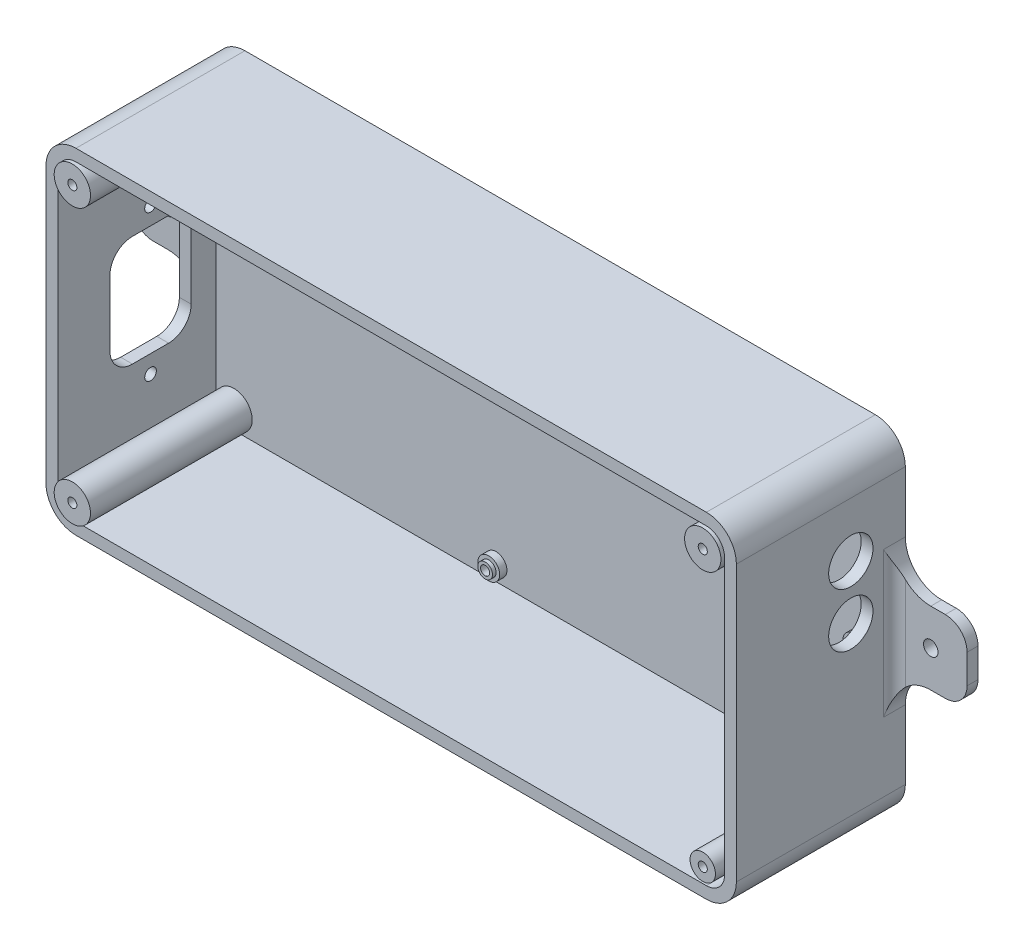
SolidWorks part; units mm, degrees
ref_plane "Front Plane" through (0, 0, 0) normal (0, 0, 1) x (1, 0, 0)
ref_plane "Top Plane" through (0, 0, 0) normal (0, 1, 0) x (1, 0, 0)
ref_plane "Right Plane" through (0, 0, 0) normal (1, 0, 0) x (0, 0, -1)
sketch "Sketch1" plane through (0, 0, 0) normal (0, 0, 1) x (1, 0, 0)
  line L0 (-68.41, 24.13) -> (105.09, 24.13)
  line L5 (-68.41, 20.88) -> (105.09, 20.88)
  line L6 (-73.41, 15.88) -> (-73.41, -59.87)
  line L7 (-68.41, -64.87) -> (105.09, -64.87)
  line L8 (110.09, 15.88) -> (110.09, -59.87)
  line L13 (113.34, 15.88) -> (113.34, -59.87)
  line L14 (-68.41, -68.12) -> (105.09, -68.12)
  line L15 (-76.66, 15.88) -> (-76.66, -59.87)
  line L16 (-73.66, 15.88) -> (-73.66, -59.87)
  line L17 (-68.41, -65.12) -> (105.09, -65.12)
  line L18 (110.34, 15.88) -> (110.34, -59.87)
  line L19 (-68.41, 21.13) -> (105.09, 21.13)
  line L25 (90.16, -25.08) -> (108.69, -25.08)
  line L26 (90.16, -25.08) -> (90.16, -55.87)
  line L27 (90.16, -55.87) -> (108.69, -55.87)
  line L28 (108.69, -25.08) -> (108.69, -55.87)
  line L29 (-0.2, 20.73) -> (88.16, 20.73)
  line L30 (-0.2, 20.73) -> (-0.2, -64.62)
  line L31 (-0.2, -64.62) -> (88.16, -64.62)
  line L32 (88.16, 20.73) -> (88.16, -64.62)
  line L33 (-44.52, 0.47) -> (-1.2, 0.47)
  line L34 (-44.52, 0.47) -> (-44.52, -63.87)
  line L35 (-44.52, -63.87) -> (-1.2, -63.87)
  line L36 (-1.2, 0.47) -> (-1.2, -63.87)
  circle A13 centre (-68.41, 15.88) radius 1.25
  circle A14 centre (105.09, 15.88) radius 1.25
  circle A15 centre (105.09, -59.87) radius 1.25
  circle A16 centre (-68.41, -59.87) radius 1.25
  arc A17 (-73.41, -59.87) -> (-68.41, -64.87) centre (-68.41, -59.87) ccw
  arc A18 (105.09, -64.87) -> (110.09, -59.87) centre (105.09, -59.87) ccw
  arc A19 (105.09, 20.88) -> (110.09, 15.88) centre (105.09, 15.88) cw
  arc A20 (-68.41, 20.88) -> (-73.41, 15.88) centre (-68.41, 15.88) ccw
  arc A21 (105.09, 24.13) -> (113.34, 15.88) centre (105.09, 15.88) cw
  arc A22 (105.09, -68.12) -> (113.34, -59.87) centre (105.09, -59.87) ccw
  arc A23 (-76.66, -59.87) -> (-68.41, -68.12) centre (-68.41, -59.87) ccw
  arc A24 (-68.41, 24.13) -> (-76.66, 15.88) centre (-68.41, 15.88) ccw
  circle A27 centre (105.09, -59.87) radius 3.5
  arc A29 (-73.66, -59.87) -> (-68.41, -65.12) centre (-68.41, -59.87) ccw
  arc A30 (105.09, -65.12) -> (110.34, -59.87) centre (105.09, -59.87) ccw
  arc A31 (105.09, 21.13) -> (110.34, 15.88) centre (105.09, 15.88) cw
  arc A32 (-68.41, 21.13) -> (-73.66, 15.88) centre (-68.41, 15.88) ccw
  circle A46 centre (104.265, -29.095) radius 2.375
  circle A47 centre (104.265, -51.465) radius 2.375
  circle A48 centre (104.265, -29.095) radius 2.175
  circle A49 centre (104.265, -51.465) radius 2.175
  circle A50 centre (104.265, -29.095) radius 1.25
  circle A51 centre (104.265, -51.465) radius 1.25
  circle A52 centre (83.915, -60.695) radius 2.225
  circle A53 centre (83.915, -14.675) radius 2.225
  circle A54 centre (3.695, -14.675) radius 2.225
  circle A55 centre (3.695, -60.695) radius 2.225
  circle A56 centre (3.695, -14.675) radius 2.025
  circle A57 centre (83.915, -14.675) radius 2.025
  circle A58 centre (83.915, -60.695) radius 2.025
  circle A59 centre (3.695, -60.695) radius 2.025
  circle A60 centre (3.695, -14.675) radius 1.25
  circle A61 centre (83.915, -14.675) radius 1.25
  circle A62 centre (83.915, -60.695) radius 1.25
  circle A63 centre (3.695, -60.695) radius 1.25
  circle A64 centre (105.09, 15.88) radius 5
  circle A65 centre (-68.41, 15.88) radius 5
  circle A66 centre (-68.41, -59.87) radius 5
  circle A67 centre (3.695, -14.675) radius 3
  circle A68 centre (83.915, -14.675) radius 3
  circle A69 centre (104.265, -29.095) radius 3.1359
  circle A70 centre (104.265, -51.465) radius 3.4191
  circle A71 centre (83.915, -60.695) radius 3
  circle A72 centre (3.695, -60.695) radius 3
  point P49 (-73.41, -64.87)
  point P58 (110.09, 20.88)
  point P61 (-73.41, 20.88)
  dimension "D3" = 73.41
  dimension "D6" = 18.53
  dimension "D7" = 30.79
  dimension "D8" = 4.75
  dimension "D9" = 4.75
  dimension "D10" = 4.425
  dimension "D11" = 4.015
  dimension "D12" = 4.405
  dimension "D13" = 0.2
  dimension "D14" = 2.5
  dimension "D15" = 2.5
  dimension "D16" = 2.5
  dimension "D17" = 2.5
  dimension "D18" = 2.5
  dimension "D19" = 2.5
  dimension "D49" = 5
  dimension "D51" = 6
  dimension "D52" = 7
  dimension "D53" = 6
  dimension "D54" = 6
  dimension "D26" = 4.45
  dimension "D27" = 4.45
  dimension "D28" = 4.45
  dimension "D29" = 4.45
  dimension "D35" = 2.5
  dimension "D36" = 2.5
  dimension "D37" = 2.5
  dimension "D38" = 2.5
  dimension "D55" = 6
  dimension "D2" = 20.88
  dimension "D20" = 1.4
  dimension "D21" = 9
  dimension "D22" = 88.36
  dimension "D23" = 85.35
  dimension "D24" = 2
  dimension "D25" = 0.25
  dimension "D30" = 4.245
  dimension "D31" = 3.895
  dimension "D32" = 3.925
  dimension "D33" = 46.02
  dimension "D34" = 0.2
  dimension "D39" = 43.32
  dimension "D40" = 64.34
  dimension "D41" = 1
  dimension "D42" = 183.5
  dimension "D43" = 85.75
  dimension "D44" = 5
  dimension "D45" = 5
  dimension "D46" = 5
  dimension "D47" = 5
  dimension "D48" = 1
  dimension "D50" = 3.25
  dimension "D56" = 3
extrude "Boss-Extrude1" add sketch "Sketch1" along normal blind 3 contours L0 A21 L13 A22 L14 A23 L15 A24
extrude "Boss-Extrude5" add sketch "Sketch1<9>" along normal blind 43.5 from surface contours L7 A18 L8 A19 L5 A20 L6 A17 | L14 A22 L13 A21 L0 A24 L15 A23 starting at face at (18.34, -21.995, 3)
sketch "Sketch1<9>" plane through (0, 0, 0) normal (0, 0, 1) x (1, 0, 0) same geometry as "Sketch1"
extrude "Boss-Extrude6" add sketch "Sketch1<10>" along normal blind 44.5 from surface contours A66 | A65 | A64 | A27 starting at face at (18.34, -21.995, 3)
sketch "Sketch1<10>" plane through (0, 0, 0) normal (0, 0, 1) x (1, 0, 0) same geometry as "Sketch1"
extrude "Boss-Extrude7" add sketch "Sketch1<11>" along normal blind 3 from surface contours A48 | A49 | A57 | A58 | A59 | A56 starting at face at (108.59, -59.87, 3)
sketch "Sketch1<11>" plane through (0, 0, 0) normal (0, 0, 1) x (1, 0, 0) same geometry as "Sketch1"
extrude "Boss-Extrude8" add sketch "Sketch1<12>" along normal blind 2 from surface contours A67 | A72 | A71 | A68 | A69 | A70 starting at face at (5.72, -14.675, 3)
sketch "Sketch1<12>" plane through (0, 0, 0) normal (0, 0, 1) x (1, 0, 0) same geometry as "Sketch1"
extrude "Cut-Extrude7" cut sketch "Sketch1<13>" along normal through all both and the other way through all contours A60 | A63 | A16 | A13 | A61 | A14 | A50 | A51 | A62 | A15
sketch "Sketch1<13>" plane through (0, 0, 0) normal (0, 0, 1) x (1, 0, 0) same geometry as "Sketch1"
sketch "Sketch3" plane through (-76.66, 0, 0) normal (-1, 0, 0) x (0, 0, 1)
  line L0 (32.16, -15.84) -> (32.16, -33.87)
  line L1 (25.96, -9.84) -> (16, -9.84)
  line L2 (31.96, -15.84) -> (31.96, -33.87)
  line L3 (25.96, -39.87) -> (16, -39.87)
  line L4 (10, -15.84) -> (10, -33.87)
  line L5 (25.96, -40.07) -> (16, -40.07)
  line L6 (9.8, -15.84) -> (9.8, -33.87)
  line L7 (25.96, -9.64) -> (16, -9.64)
  line L8 (0, 15.88) -> (0, -59.87) construction
  line L9 (46.5, -59.87) -> (0, -59.87) construction
  arc A0 (16, -39.87) -> (10, -33.87) centre (16, -33.87) cw
  arc A1 (16, -9.84) -> (10, -15.84) centre (16, -15.84) ccw
  arc A2 (25.96, -9.84) -> (31.96, -15.84) centre (25.96, -15.84) cw
  arc A3 (31.96, -33.87) -> (25.96, -39.87) centre (25.96, -33.87) cw
  circle A4 centre (20.98, -44.95) radius 1.6
  circle A5 centre (20.98, -4.76) radius 1.6
  arc A6 (32.16, -33.87) -> (25.96, -40.07) centre (25.96, -33.87) cw
  arc A7 (16, -40.07) -> (9.8, -33.87) centre (16, -33.87) cw
  arc A8 (16, -9.64) -> (9.8, -15.84) centre (16, -15.84) ccw
  arc A9 (25.96, -9.64) -> (32.16, -15.84) centre (25.96, -15.84) cw
  point P8 (10, -9.84)
  point P11 (31.96, -9.84)
  point P14 (31.96, -39.87)
  point P19 (0, 0)
  point P20 (0, 0)
  point P21 (0, 0)
  point P24 (29.5662, -30.03)
  dimension "D3" = 6
  dimension "D4" = 3.2
  dimension "D5" = 3.2
  dimension "D1" = 21.96
  dimension "D2" = 30.03
  dimension "D6" = 40.19
  dimension "D7" = 5.08
  dimension "D8" = 10.98
  dimension "D10" = 10
  dimension "D11" = 20
  dimension "D9" = 0.2
extrude "Cut-Extrude8" cut sketch "Sketch3" against normal up to next and the other way through all contours A5 | A4 | L5 A7 L6 A8 L7 A9 L0 A6
sketch "Sketch4" plane through (113.34, 0, 0) normal (1, 0, 0) x (0, 0, -1)
  line L0 (-46.5, 15.88) -> (0, 15.88) construction
  line L1 (0, 15.88) -> (0, -59.87) construction
  circle A0 centre (-15, 0.88) radius 4.16
  circle A1 centre (-15, -14.05) radius 4.16
  circle A2 centre (-15, 0.88) radius 6.1
  circle A3 centre (-15, -14.05) radius 6.1
  dimension "D1" = 8.32
  dimension "D2" = 8.32
  dimension "D4" = 12.2
  dimension "D5" = 12.2
  dimension "D3" = 14.93
  dimension "D6" = 15
  dimension "D7" = 15
extrude "Cut-Extrude9" cut sketch "Sketch4" against normal up to next contours A3 | A2
sketch "Sketch5" plane through (0, 0, 0) normal (0, 0, -1) x (-1, 0, 0)
  line L0 (76.66, 15.88) -> (76.66, -59.87) construction
  line L1 (76.66, -10.87) -> (90.66, -10.87)
  line L2 (76.66, -10.87) -> (76.66, -30.87)
  line L3 (76.66, -30.87) -> (90.66, -30.87)
  line L4 (96.66, -16.87) -> (96.66, -24.87)
  line L5 (-113.34, 15.88) -> (-113.34, -59.87) construction
  line L6 (-113.34, -10.87) -> (-127.34, -10.87)
  line L7 (-113.34, -10.87) -> (-113.34, -30.87)
  line L8 (-113.34, -30.87) -> (-127.34, -30.87)
  line L9 (-133.34, -16.87) -> (-133.34, -24.87)
  line L10 (68.41, 24.13) -> (-105.09, 24.13) construction
  arc A0 (-127.34, -30.87) -> (-133.34, -24.87) centre (-127.34, -24.87) cw
  arc A1 (-127.34, -10.87) -> (-133.34, -16.87) centre (-127.34, -16.87) ccw
  arc A2 (90.66, -30.87) -> (96.66, -24.87) centre (90.66, -24.87) ccw
  arc A3 (90.66, -10.87) -> (96.66, -16.87) centre (90.66, -16.87) cw
  circle A4 centre (-123.34, -20.87) radius 2
  circle A5 centre (86.66, -20.87) radius 2
  point P16 (-133.34, -30.87)
  point P19 (-133.34, -10.87)
  point P24 (96.66, -10.87)
  point P29 (0, 0)
  dimension "D5" = 6
  dimension "D9" = 4
  dimension "D10" = 4
  dimension "D1" = 20
  dimension "D2" = 20
  dimension "D3" = 20
  dimension "D4" = 35
  dimension "D6" = 10
  dimension "D7" = 10
  dimension "D8" = 10
extrude "Boss-Extrude9" add sketch "Sketch5" against normal blind 3
fillet "Fillet2" radius 10 4 edges at (113.34, -30.87, 1.5) (113.34, -10.87, 1.5) (-76.66, -10.87, 1.5) (-76.66, -30.87, 1.5)
fillet "Fillet3" radius 3 2 edges at (-76.66, -20.87, 3) (113.34, -20.87, 3)
